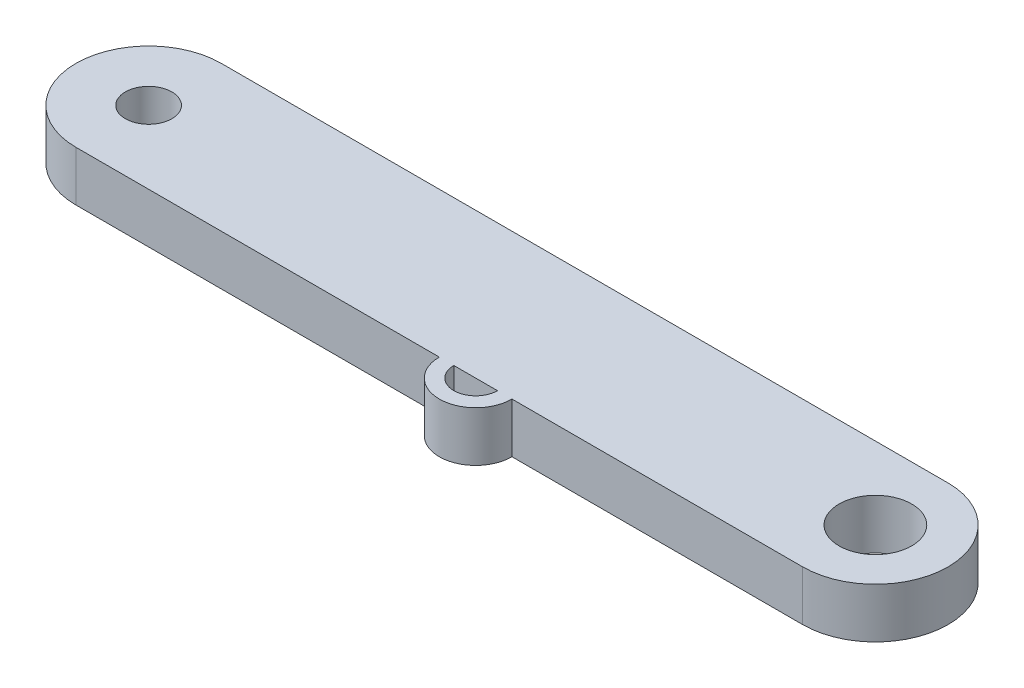
SolidWorks part; units mm, degrees
ref_plane "Alzado" through (0, 0, 0) normal (0, 0, 1) x (1, 0, 0)
ref_plane "Planta" through (0, 0, 0) normal (0, 1, 0) x (1, 0, 0)
ref_plane "Vista lateral" through (0, 0, 0) normal (1, 0, 0) x (0, 0, -1)
sketch "Croquis1" plane through (0, 0, 0) normal (0, 1, 0) x (1, 0, 0)
  line L7 (-50, -10) -> (50, -10)
  line L10 (-50, 10) -> (50, 10)
  line L11 (-50, 0) -> (50, 0) construction
  line L12 (-53.2, 0) -> (-53.2, 44.7716) construction
  line L13 (-60, 0) -> (-60, 44.7716) construction
  line L14 (-46.8, 0) -> (-46.8, 44.7716) construction
  arc A0 (50, 10) -> (50, -10) centre (50, 0) cw
  arc A1 (-50, -10) -> (-50, 10) centre (-50, 0) cw
  circle A3 centre (-50, 0) radius 3.2
  circle A8 centre (50, 0) radius 5
  dimension "D3" = 6.4
  dimension "D4" = 6.8
  dimension "D6" = 10
  dimension "D1" = 100
  dimension "D2" = 20
  dimension "D5" = 13.2
extrude "Saliente-Extruir2" add sketch "Croquis1" along normal blind 6.88 contours A1 L7 A0 L10 A3 region at (-1.0522, 0, 0)
sketch "Croquis3" plane through (0, 0, 0) normal (0, 1, 0) x (1, 0, 0)
  line L2 (-50, -10) -> (50, -10) construction
  line L3 (0, -10) -> (2, -10)
  line L4 (0, -10) -> (2, -10)
  line L5 (8, -10) -> (10, -10)
  line L6 (-50, 0) -> (0, -10) construction
  line L7 (8, -10) -> (10, -10)
  arc A2 (2, -10) -> (8, -10) centre (5, -10) ccw
  arc A3 (0, -10) -> (10, -10) centre (5, -10) ccw
  dimension "D1" = 3
  dimension "D3" = 50
  dimension "D2" = 2
extrude "Saliente-Extruir3" add sketch "Croquis3" along normal up to surface (6.88 mm away) contours L3 A3 A2 region at (1, 0, 10.1118) up to face at (50, 6.88, 5)
